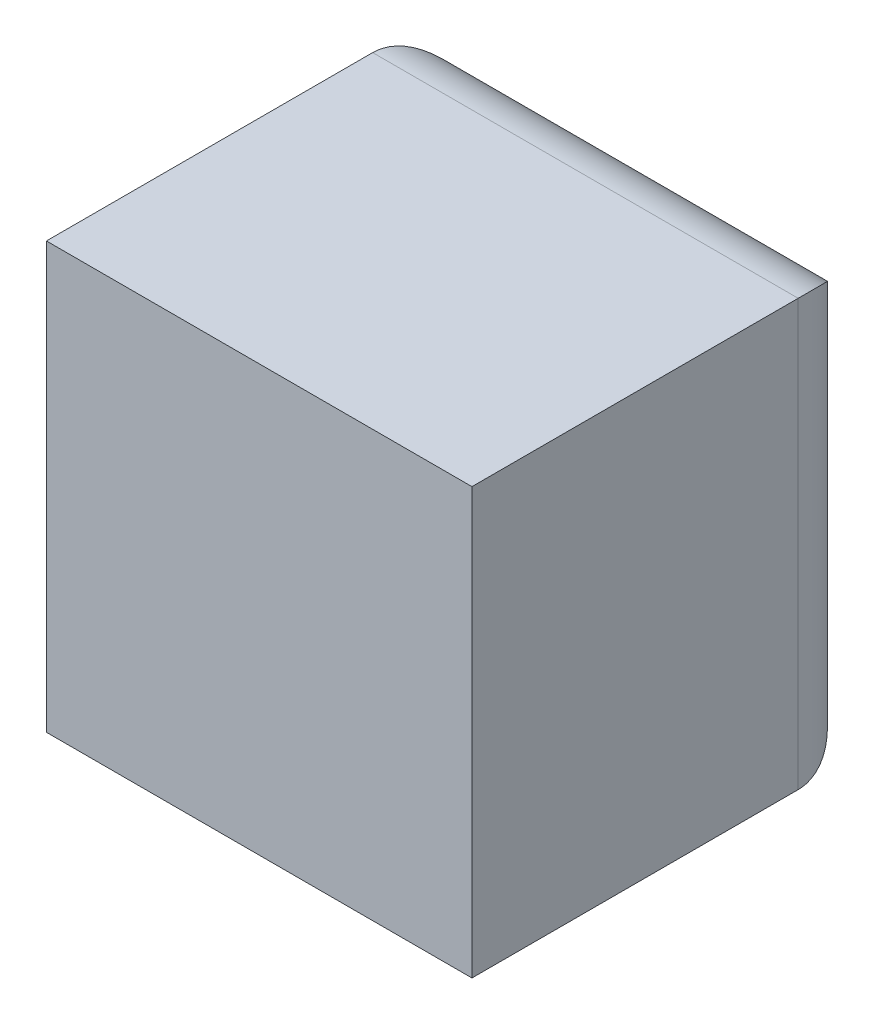
SolidWorks part; units mm, degrees
ref_plane "Front Plane" through (0, 0, 0) normal (0, 0, 1) x (1, 0, 0)
ref_plane "Top Plane" through (0, 0, 0) normal (0, 1, 0) x (1, 0, 0)
ref_plane "Right Plane" through (0, 0, 0) normal (1, 0, 0) x (0, 0, -1)
sketch "Sketch1" plane through (0, 0, 0) normal (0, 0, 1) x (1, 0, 0)
  line L1 (0, 0) -> (15, 0)
  line L2 (0, 0) -> (0, 15)
  line L3 (0, 15) -> (15, 15)
  line L4 (15, 0) -> (15, 15)
  dimension "D1" = 15
  dimension "D2" = 15
extrude "Boss-Extrude1" add sketch "Sketch1" along normal blind 14
fillet "Fillet2" radius 2.5 4 edges at (7.5, 0, 0) (15, 7.5, 0) (7.5, 15, 0) (0, 7.5, 0)
